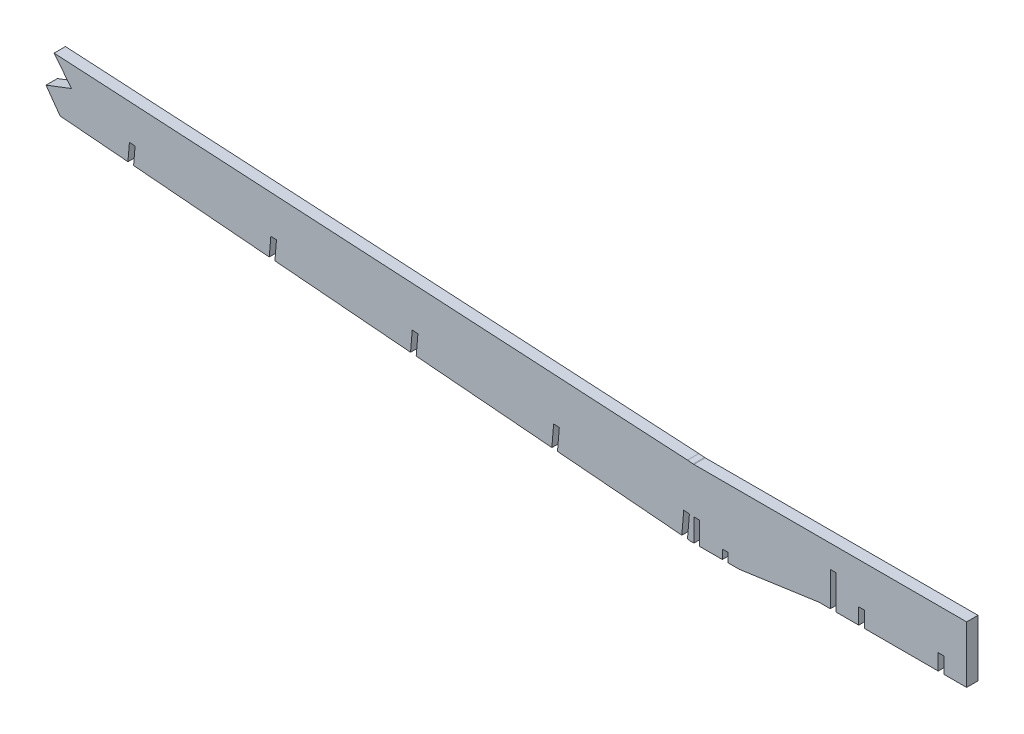
SolidWorks part; units mm, degrees
material "Balsa"
ref_plane "Front Plane" through (0, 0, 0) normal (0, 0, 1) x (1, 0, 0)
ref_plane "Top Plane" through (0, 0, 0) normal (0, 1, 0) x (1, 0, 0)
ref_plane "Right Plane" through (0, 0, 0) normal (1, 0, 0) x (0, 0, -1)
sketch "Sketch1" plane through (0, 0, 0) normal (0, 0, 1) x (1, 0, 0)
  line L0 (76.2, 56.7475) -> (76.2, 37.6975)
  line L1 (79.375, 56.7475) -> (79.375, 37.6975)
  line L2 (0, 44.0475) -> (0, 31.3475)
  line L3 (3.175, 44.0475) -> (3.175, 31.3475)
  line L4 (-5.7133, 44.4467) -> (-6.776, 31.7912)
  line L5 (-2.5494, 44.181) -> (-3.6121, 31.5255)
  line L6 (-1.4923, 31.3475) -> (25.4, 31.3475)
  line L7 (25.4, 31.3475) -> (69.85, 37.6975)
  line L8 (-2.5494, 44.181) -> (-0.424, 69.4919) construction
  line L9 (-0.424, 69.4919) -> (-3.5879, 69.7576)
  line L10 (-3.5879, 69.7576) -> (-5.7133, 44.4467) construction
  line L11 (-5.7133, 44.4467) -> (-2.5494, 44.181)
  line L12 (3.175, 44.0475) -> (3.175, 69.4475) construction
  line L13 (3.175, 69.4475) -> (0, 69.4475)
  line L14 (0, 69.4475) -> (0, 44.0475) construction
  line L15 (0, 44.0475) -> (3.175, 44.0475)
  line L16 (92.075, 37.6975) -> (92.075, 46.5875)
  line L17 (-942.8808, 122.7744) -> (-947.5199, 67.5279)
  line L18 (0, 69.4475) -> (-0.424, 69.4919)
  line L19 (3.175, 69.4475) -> (152.4, 69.4475)
  line L20 (152.4, 69.4475) -> (152.4, 37.6975)
  line L21 (152.4, 37.6975) -> (69.85, 37.6975)
  line L22 (92.075, 46.5875) -> (95.25, 46.5875)
  line L23 (95.25, 46.5875) -> (95.25, 37.6975)
  line L24 (-1.4923, 31.3475) -> (-943.9128, 110.4848)
  line L25 (79.375, 69.4475) -> (79.375, 56.7475)
  line L26 (-942.8808, 122.7744) -> (-3.5879, 69.7576)
  line L27 (136.525, 37.6975) -> (136.525, 46.5875)
  line L28 (76.2, 69.4475) -> (76.2, 56.7475)
  line L29 (79.375, 56.7475) -> (76.2, 56.7475)
  line L30 (-943.5688, 114.5813) -> (-5.7133, 44.4467)
  line L31 (136.525, 46.5875) -> (139.7, 46.5875)
  line L32 (139.7, 46.5875) -> (139.7, 37.6975)
  line L33 (15.875, 31.3475) -> (15.875, 36.4275)
  line L34 (15.875, 36.4275) -> (19.05, 36.4275)
  line L35 (19.05, 36.4275) -> (19.05, 31.3475)
  line L36 (-942.8808, 122.7744) -> (-946.0519, 122.9534)
  line L37 (-946.0519, 122.9534) -> (-946.5835, 116.6233)
  line L38 (-946.5835, 116.6233) -> (-943.4123, 116.4443)
  dimension "D3" = 76.2
  dimension "D10" = 12.3329
  dimension "D11" = 8.2219
  dimension "D2" = 25.4
  dimension "D4" = 25.4
  dimension "D5" = 12.7
  dimension "D7" = 3.175
  dimension "D9" = 3.175
  dimension "D12" = 3.175
  dimension "D6" = 19.05
  dimension "D13" = 6.35
  dimension "D14" = 12.7
  dimension "D16" = 3.175
  dimension "D17" = 3.175
  dimension "D18" = 12.7
  dimension "D19" = 12.7
  dimension "D20" = 8.89
  dimension "D21" = 8.89
  dimension "D15" = 76.2
  dimension "D22" = 12.7
  dimension "D23" = 3.175
  dimension "D24" = 5.08
  dimension "D8" = 6.35
  dimension "D25" = 3.175
  dimension "D26" = 6.35
extrude "Boss-Extrude1" add sketch "Sketch1" along normal mid plane 6.35 contours L17 L30 L11 L5 L24 L6 L2 L15 L3 L7 L21 L0 L28 L19 L13 L18 L9 L26 | L30 L17 L24 L4 | L29 L25 L19 L28 | L19 L25 L1 L21 L20 | L37 L38 L17 L36 region at (-328.9931, 77.9728, 0) region at (77.7875, 63.0975, 0) region at (115.8875, 53.8578, 0) region at (-944.7321, 119.6988, 0) region at (-395.1618, 68.9894, 0)
sketch "Sketch2" plane through (0, 0, 3.175) normal (0, 0, 1) x (1, 0, 0)
  line L2 (-73.2652, 73.2231) -> (-80.3969, -11.7061)
  line L3 (-943.5688, 114.5813) -> (-5.7133, 44.4467)
  line L6 (-76.4291, 73.4888) -> (-83.5608, -11.4404)
  line L7 (-6.776, 31.7912) -> (-943.9128, 110.4848)
  line L10 (-152.4177, 77.6821) -> (-159.3225, -4.5442)
  line L14 (-155.5816, 77.9478) -> (-162.4863, -4.2785)
  line L18 (-231.5658, 82.1932) -> (-238.251, 2.5812)
  line L22 (-234.7297, 82.4589) -> (-241.4149, 2.8469)
  line L26 (-310.7178, 86.6582) -> (-317.1769, 9.7387)
  line L30 (-313.8817, 86.9239) -> (-320.3408, 10.0043)
  line L34 (-389.8657, 91.1713) -> (-396.1056, 16.8623)
  line L38 (-393.0296, 91.437) -> (-399.2695, 17.128)
  line L42 (-469.0186, 95.6263) -> (-475.031, 24.0265)
  line L46 (-472.1824, 95.892) -> (-478.1948, 24.2921)
  line L50 (-548.1666, 100.1381) -> (-553.9596, 31.1506)
  line L54 (-551.3305, 100.4038) -> (-557.1235, 31.4163)
  line L58 (-627.3195, 104.5918) -> (-632.8849, 38.3152)
  line L62 (-630.4834, 104.8575) -> (-636.0488, 38.5809)
  line L66 (-706.4673, 109.1069) -> (-711.8138, 45.4365)
  line L70 (-709.6312, 109.3725) -> (-714.9777, 45.7022)
  line L74 (-785.6206, 113.5558) -> (-790.7389, 52.6041)
  line L78 (-788.7845, 113.8214) -> (-793.9027, 52.8697)
  line L82 (-864.7684, 118.071) -> (-869.6679, 59.7246)
  line L86 (-867.9323, 118.3366) -> (-872.8317, 59.9902)
  line L89 (-942.9091, 122.4365) -> (-947.5795, 66.8182)
  line M2 (-943.9128, 110.4848) -> (-6.776, 31.7912)
extrude "Cut-Extrude1" cut sketch "Sketch2" against normal through all contours L3 L6 L2 M2 | L3 L14 L7 L10 | L3 L22 L7 L18 | L3 L30 L7 L26 | L3 L38 L7 L34 | L3 L46 L7 L42 | L3 L54 L7 L50 | L3 L62 L7 L58 | L3 L70 L7 L66 | L3 L78 L7 L74 | L3 L86 L7 L82 region at (-77.3317, 43.7615, 3.175) region at (-156.332, 50.0322, 3.175) region at (-235.3323, 56.3029, 3.175) region at (-314.3326, 62.5736, 3.175) region at (-393.3328, 68.8442, 3.175) region at (-472.3331, 75.1149, 3.175) region at (-551.3334, 81.3856, 3.175) region at (-630.3336, 87.6563, 3.175) region at (-709.3339, 93.9269, 3.175) region at (-788.334, 100.1976, 3.175) region at (-867.3342, 106.4683, 3.175)
sketch "Sketch3" plane through (0, 0, 3.175) normal (0, 0, 1) x (1, 0, 0)
  line L0 (-354.2316, 60.9679) -> (-362.1267, 71.9794)
  line L1 (-316.3285, 57.7851) -> (-392.1347, 64.1507) construction
  line L2 (-362.1267, 71.9794) -> (-347.8724, 77.4491)
  line L3 (-347.8724, 77.4491) -> (-357.599, 89.7392)
  line L4 (-946.0519, 122.9534) -> (-3.5879, 69.7576) construction
  line L5 (-357.599, 89.7392) -> (-993.7912, 254.1833)
  line L6 (-993.7912, 254.1833) -> (-993.7912, 28.7351)
  line L7 (-993.7912, 28.7351) -> (-354.2316, 60.9679)
extrude "Cut-Extrude2" cut sketch "Sketch3" against normal blind 7.62
equation "\"D11@Sketch1\"=\"D10@Sketch1\"*(2/3)"
